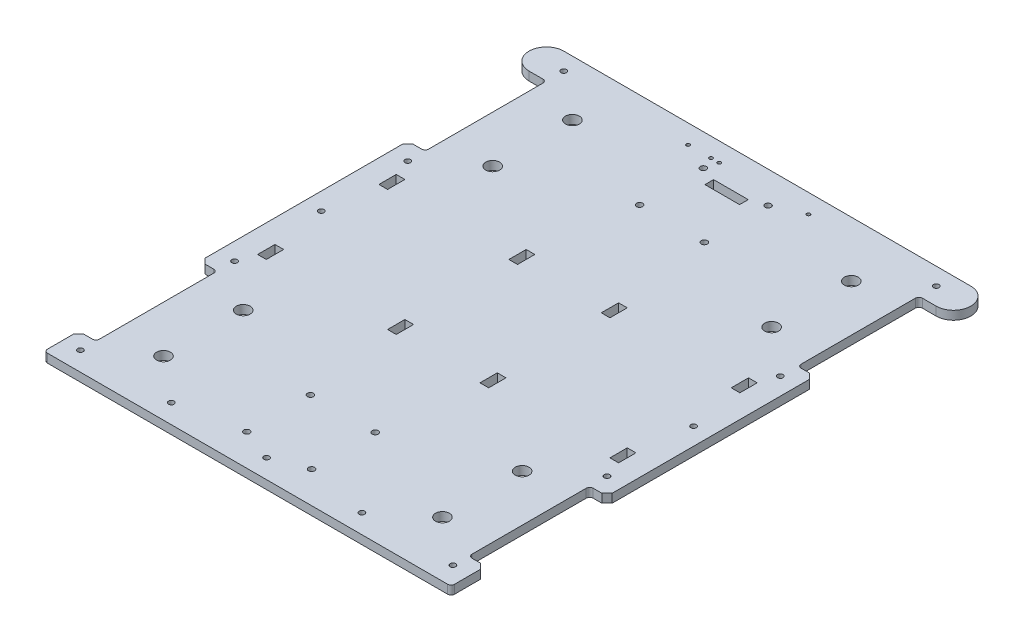
SolidWorks part; units mm, degrees
material "Teak"
ref_plane "Front Plane" through (0, 0, 0) normal (0, 0, 1) x (1, 0, 0)
ref_plane "Top Plane" through (0, 0, 0) normal (0, 1, 0) x (1, 0, 0)
ref_plane "Right Plane" through (0, 0, 0) normal (1, 0, 0) x (0, 0, -1)
sketch "Sketch1" plane through (0, 0, 0) normal (0, 1, 0) x (1, 0, 0)
  line L0 (0, 170) -> (0, -130) construction
  line L1 (-117.5, 0) -> (117.5, 0) construction
  line L2 (-117.5, -130) -> (117.5, -130)
  line L3 (117.5, -130) -> (117.5, -110)
  line L4 (117.5, -110) -> (107.5, -110)
  line L5 (107.5, -110) -> (107.5, -40)
  line L6 (107.5, -40) -> (117.5, -40)
  line L7 (117.5, -40) -> (117.5, 80)
  line L8 (117.5, 80) -> (107.5, 80)
  line L9 (107.5, 80) -> (107.5, 150)
  line L10 (107.5, 150) -> (127.5, 150)
  line L11 (-107.5, 150) -> (-127.5, 150)
  line L12 (-107.5, 80) -> (-107.5, 150)
  line L13 (-117.5, 80) -> (-107.5, 80)
  line L14 (-117.5, -40) -> (-117.5, 80)
  line L15 (-107.5, -40) -> (-117.5, -40)
  line L16 (-107.5, -110) -> (-107.5, -40)
  line L17 (-117.5, -110) -> (-107.5, -110)
  line L18 (-117.5, -130) -> (-117.5, -110)
  line L19 (127.5, 150) -> (127.5, 170)
  line L20 (127.5, 170) -> (-127.5, 170)
  line L21 (-127.5, 150) -> (-127.5, 170)
  point P5 (0, 0)
  dimension "D1" = 300
  dimension "D2" = 20
  dimension "D3" = 20
  dimension "D5" = 10
  dimension "D6" = 70
  dimension "D7" = 70
  dimension "D8" = 255
  dimension "D9" = 20
extrude "Boss-Extrude1" add sketch "Sketch1" along normal blind 5
fillet "Fillet3" 2 edges at (127.5, 2.5, -150) (127.5, 2.5, -170) type full round first side face at (117.5, 2.5, -150) second side face at (0, 2.5, -170) middle face at (127.5, 2.5, -160)
fillet "Fillet4" 2 edges at (-127.5, 2.5, -170) (-127.5, 2.5, -150) type full round first side face at (-5, 2.5, -170) second side face at (-117.5, 2.5, -150) middle face at (-127.5, 2.5, -160)
fillet "Fillet2" radius 2 10 edges at (107.5, 2.5, 40) (107.5, 2.5, -150) (107.5, 2.5, -80) (107.5, 2.5, 110) (-107.5, 2.5, -80) (-107.5, 2.5, 110) (-107.5, 2.5, 40) (-107.5, 2.5, -150) (-117.5, 2.5, 130) (117.5, 2.5, 130)
sketch "Sketch2" plane through (0, 5, 0) normal (0, 1, 0) x (1, 0, 0)
  line L0 (0, -130) -> (0, 90) construction
  line L1 (-115.5, -130) -> (115.5, -130) construction
  line L2 (107.5, 82) -> (107.5, 148) construction
  line L4 (117.5, -40) -> (117.5, 80) construction
  line L5 (117.5, -128) -> (117.5, -110) construction
  arc A0 (117.5, 150) -> (117.5, 170) centre (117.5, 160) ccw construction
  circle A1 centre (107.5, 160) radius 1.6
  circle A2 centre (107.5, 20) radius 1.6
  circle A3 centre (107.5, -119) radius 1.6
  circle A4 centre (0, -119) radius 1.6
  circle A5 centre (-107.5, -119) radius 1.6
  circle A6 centre (-107.5, 20) radius 1.6
  circle A7 centre (-107.5, 160) radius 1.6
  circle A8 centre (55, -119) radius 1.6
  circle A9 centre (-55, -119) radius 1.6
  circle A10 centre (-107.5, 70) radius 1.6
  circle A11 centre (107.5, 70) radius 1.6
  circle A12 centre (-107.5, -30) radius 1.6
  circle A13 centre (107.5, -30) radius 1.6
  point P17 (127.5, 160)
  point P26 (117.5, 20)
  point P30 (117.5, -119)
  dimension "D1" = 3.2
  dimension "D2" = 2
  dimension "D3" = 10
  dimension "D4" = 2
  dimension "D5" = 2
  dimension "D6" = 2
  dimension "D7" = 2
extrude "layer fix hole" cut sketch "Sketch2" against normal through all
chamfer "Chamfer1" distance 3 angle 45 6 edges at (117.5, 2.5, 110) (-117.5, 2.5, -80) (-117.5, 2.5, 40) (-117.5, 2.5, 110) (117.5, 2.5, -80) (117.5, 2.5, 40)
sketch "Sketch9" plane through (0, 0, 0) normal (0, -1, 0) x (1, 0, 0)
  line L0 (107.5, -115) -> (-119.4618, -115) construction
  line L1 (107.5, -82) -> (107.5, -148) construction
  line L2 (107.5, 75) -> (-117.246, 75) construction
  line L3 (107.5, 108) -> (107.5, 42) construction
  line L4 (-117.5, -20) -> (128.0189, -20) construction
  line L5 (0, 75) -> (0, -115) construction
  line L6 (-80.5, -96.3983) -> (-80.5, -133.6017) construction
  line L7 (-107.5, -148) -> (-107.5, -82) construction
  line L8 (-117.5, -77) -> (-117.5, 37) construction
  circle A0 centre (-80.5, -138) radius 4
  circle A1 centre (-80.5, -92) radius 4
  circle A2 centre (80.5, -92) radius 4
  circle A3 centre (80.5, -138) radius 4
  circle A4 centre (80.5, 98) radius 4
  circle A5 centre (80.5, 52) radius 4
  circle A6 centre (-80.5, 98) radius 4
  circle A7 centre (-80.5, 52) radius 4
  point P16 (-80.5, -115)
  dimension "D2" = 8
  dimension "D1" = 27
  dimension "D3" = 23
extrude "Motor fix hole" cut sketch "Sketch9" against normal up to next
sketch "Sketch10" plane through (0, 0, 0) normal (0, -1, 0) x (1, 0, 0)
  line L0 (-117.5, -20) -> (130.9103, -20) construction
  line L1 (-117.5, -77) -> (-117.5, 37) construction
  line L2 (0, 130) -> (0, -170) construction
  line L3 (-115.5, 130) -> (115.5, 130) construction
  line L4 (117.5, -170) -> (-117.5, -170) construction
  line L5 (-18.6898, 75) -> (18.6898, 75) construction
  line L6 (-23.6898, 116.7418) -> (23.6898, 116.7418) construction
  line L7 (-23.6898, 116.7418) -> (-23.6898, 70) construction
  line L8 (-23.6898, 70) -> (23.6898, 70) construction
  line L9 (23.6898, 116.7418) -> (23.6898, 70) construction
  line L10 (-23.6898, 116.7418) -> (23.6898, 70) construction
  line L11 (-23.6898, 70) -> (23.6898, 116.7418) construction
  line L12 (18.6898, 111.7418) -> (18.6898, 75) construction
  line L13 (-18.6898, 111.7418) -> (18.6898, 111.7418) construction
  line L14 (-18.6898, 111.7418) -> (-18.6898, 75) construction
  line L18 (-18.6898, -151.7418) -> (-18.6898, -115) construction
  line L19 (-18.6898, -151.7418) -> (18.6898, -151.7418) construction
  line L25 (18.6898, -151.7418) -> (18.6898, -115) construction
  line L28 (-23.6898, -110) -> (23.6898, -156.7418) construction
  line L30 (-23.6898, -156.7418) -> (23.6898, -110) construction
  line L32 (23.6898, -156.7418) -> (23.6898, -110) construction
  line L33 (-23.6898, -110) -> (23.6898, -110) construction
  line L34 (-23.6898, -156.7418) -> (-23.6898, -110) construction
  line L36 (-23.6898, -156.7418) -> (23.6898, -156.7418) construction
  line L37 (-18.6898, -115) -> (18.6898, -115) construction
  circle A0 centre (18.6898, 75) radius 1.75
  circle A1 centre (-18.6898, 75) radius 1.75
  circle A2 centre (-18.6898, 111.7418) radius 1.75
  circle A3 centre (18.6898, 111.7418) radius 1.75
  circle A4 centre (18.6898, -151.7418) radius 1.75
  circle A5 centre (-18.6898, -151.7418) radius 1.75
  circle A6 centre (-18.6898, -115) radius 1.75
  circle A7 centre (18.6898, -115) radius 1.75
  point P10 (0, 93.3709)
  point P23 (0, 0)
  point P24 (0, -115)
  point P37 (0, -133.3709)
  point P38 (0, 89.9075)
  dimension "D3" = 3.5
  dimension "D1" = 37.3795
  dimension "D2" = 5
  dimension "D4" = 36.7418
  dimension "D5" = 90
extrude "Motor driver fix hole" cut sketch "Sketch10" against normal up to next
sketch "Sketch11" plane through (0, 0, 0) normal (0, -1, 0) x (1, 0, 0)
  line L0 (0, -170) -> (0, -144.1108) construction
  line L1 (117.5, -170) -> (-117.5, -170) construction
  line L2 (0, -144.1108) -> (0, -110.0028) construction
  line L5 (-37.465, -159) -> (37.465, -159) construction
  line L7 (34.2319, -158.1371) -> (37.465, -159) construction
  line L8 (-37.465, -159) -> (-34.2319, -158.1371) construction
  line L10 (-10, -144) -> (10, -144)
  line L11 (-10, -144) -> (-10, -149)
  line L12 (-10, -149) -> (10, -149)
  line L13 (10, -144) -> (10, -149)
  line L14 (-10, -144) -> (10, -149) construction
  line L15 (-10, -149) -> (10, -144) construction
  circle A0 centre (-34.7373, -159) radius 1
  circle A1 centre (-21.5138, -159) radius 1
  circle A2 centre (-16.8148, -159) radius 1
  circle A3 centre (34.7373, -159) radius 1
  point P1 (0, -146.5)
  point P5 (0, -149.001)
  dimension "D2" = 2.7277
  dimension "D6" = 2
  dimension "D1" = 2.7277
  dimension "D3" = 13.2235
  dimension "D4" = 4.699
  dimension "D5" = 51.5521
  dimension "D7" = 20
  dimension "D8" = 5
  dimension "D9" = 11
  dimension "D10" = 10
extrude "QTR8a fix hole" cut sketch "Sketch11" against normal blind 10
sketch "Sketch 12" plane through (0, 5, 0) normal (0, 1, 0) x (1, 0, 0)
  line L0 (-39.1667, 170) -> (-39.1667, -135.4982) construction
  line L1 (117.5, 170) -> (-117.5, 170) construction
  line L2 (-117.5, 20) -> (117.5, 20) construction
  line L12 (24.1667, 60) -> (29.1667, 60)
  line L37 (-117.5, -120.5) -> (-39.1667, -120.5) construction
  line L38 (39.1667, 170) -> (39.1667, -135.4982) construction
  line L39 (-39.1667, -120.5) -> (39.1667, -120.5) construction
  line L40 (39.1667, -120.5) -> (117.5, -120.5) construction
  line L41 (117.5, -128) -> (117.5, -113) construction
  line L42 (-117.5, -113) -> (-117.5, -128) construction
  line L43 (99.1667, 60) -> (99.1667, 50)
  line L44 (24.1667, 60) -> (24.1667, 50)
  line L45 (24.1667, 50) -> (29.1667, 50)
  line L46 (29.1667, 60) -> (29.1667, 50)
  line L86 (-117.5, 77) -> (-117.5, -37) construction
  line L87 (117.5, -37) -> (117.5, 77) construction
  line L88 (24.1667, -10) -> (29.1667, -10)
  line L89 (29.1667, -20) -> (29.1667, -10)
  line L90 (24.1667, -20) -> (29.1667, -20)
  line L91 (24.1667, -20) -> (24.1667, -10)
  line L92 (99.1667, 60) -> (104.1667, 60)
  line L93 (104.1667, 60) -> (104.1667, 50)
  line L94 (99.1667, 50) -> (104.1667, 50)
  line L95 (99.1667, -10) -> (104.1667, -10)
  line L96 (104.1667, -20) -> (104.1667, -10)
  line L97 (99.1667, -20) -> (104.1667, -20)
  line L98 (99.1667, -20) -> (99.1667, -10)
  line L99 (-104.1667, 60) -> (-99.1667, 60)
  line L100 (-29.1667, 60) -> (-29.1667, 50)
  line L101 (-104.1667, 60) -> (-104.1667, 50)
  line L102 (-104.1667, 50) -> (-99.1667, 50)
  line L103 (-99.1667, 60) -> (-99.1667, 50)
  line L104 (-104.1667, -10) -> (-99.1667, -10)
  line L105 (-99.1667, -20) -> (-99.1667, -10)
  line L106 (-104.1667, -20) -> (-99.1667, -20)
  line L107 (-104.1667, -20) -> (-104.1667, -10)
  line L108 (-29.1667, 60) -> (-24.1667, 60)
  line L109 (-24.1667, 60) -> (-24.1667, 50)
  line L110 (-29.1667, 50) -> (-24.1667, 50)
  line L111 (-29.1667, -10) -> (-24.1667, -10)
  line L112 (-24.1667, -20) -> (-24.1667, -10)
  line L113 (-29.1667, -20) -> (-24.1667, -20)
  line L114 (-29.1667, -20) -> (-29.1667, -10)
  line L115 (-245.8333, 20) -> (-10.8333, 20) construction
  line L117 (-89.1667, 170) -> (-89.1667, -135.4982) construction
  point P0 (29.1667, 55)
  dimension "D1" = 5
  dimension "D2" = 10
  dimension "D3" = 10
  dimension "D4" = 2
  dimension "D7" = 60
  dimension "D8" = 10
  dimension "D5" = 2
  dimension "D6" = 70
extrude "Battery fixed hole" cut sketch "Sketch 12" against normal through all
